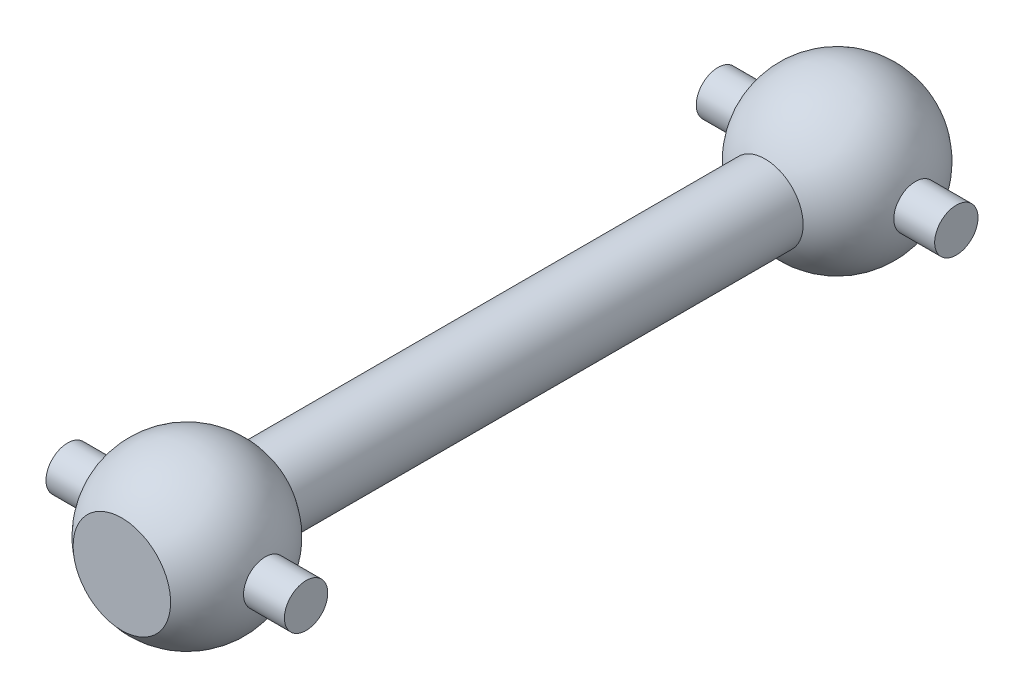
SolidWorks part; units mm, degrees
material "7075-O (SS)"
ref_plane "前视基准面" through (0, 0, 0) normal (0, 0, 1) x (1, 0, 0)
ref_plane "上视基准面" through (0, 0, 0) normal (0, 1, 0) x (1, 0, 0)
ref_plane "右视基准面" through (0, 0, 0) normal (1, 0, 0) x (0, 0, -1)
sketch "草图1" plane through (0, 0, 0) normal (0, 0, 1) x (1, 0, 0)
  circle A0 centre (0, 0) radius 3.5
  dimension "D1" = 7
extrude "凸台-拉伸1" add sketch "草图1" along normal mid plane 50
sketch "草图2" plane through (0, 0, 0) normal (1, 0, 0) x (0, 0, -1)
  line L0 (25, -3.5) -> (25, 3.5) construction
  line L1 (36, 4.5) -> (36, -4.5)
  line L2 (22.5, 0) -> (36, 0)
  circle A0 centre (30, 0) radius 7.5
  dimension "D1" = 15
  dimension "D2" = 5
  dimension "D3" = 36
revolve "旋转1" add sketch "草图2" angle 360 about L2 region at (0, 3.2638, -29.6374)
sketch "草图3" plane through (0, 0, 0) normal (1, 0, 0) x (0, 0, -1)
  circle A0 centre (30, 0) radius 2
  arc A1 (36, 4.5) -> (23.3668, 3.5) centre (30, 0) ccw construction
  dimension "D1" = 4
extrude "凸台-拉伸2" add sketch "草图3" along normal mid plane 22
mirror "镜向1" about plane through (0, 0, 0) normal (0, 0, 1) of "凸台-拉伸2", "旋转1"
